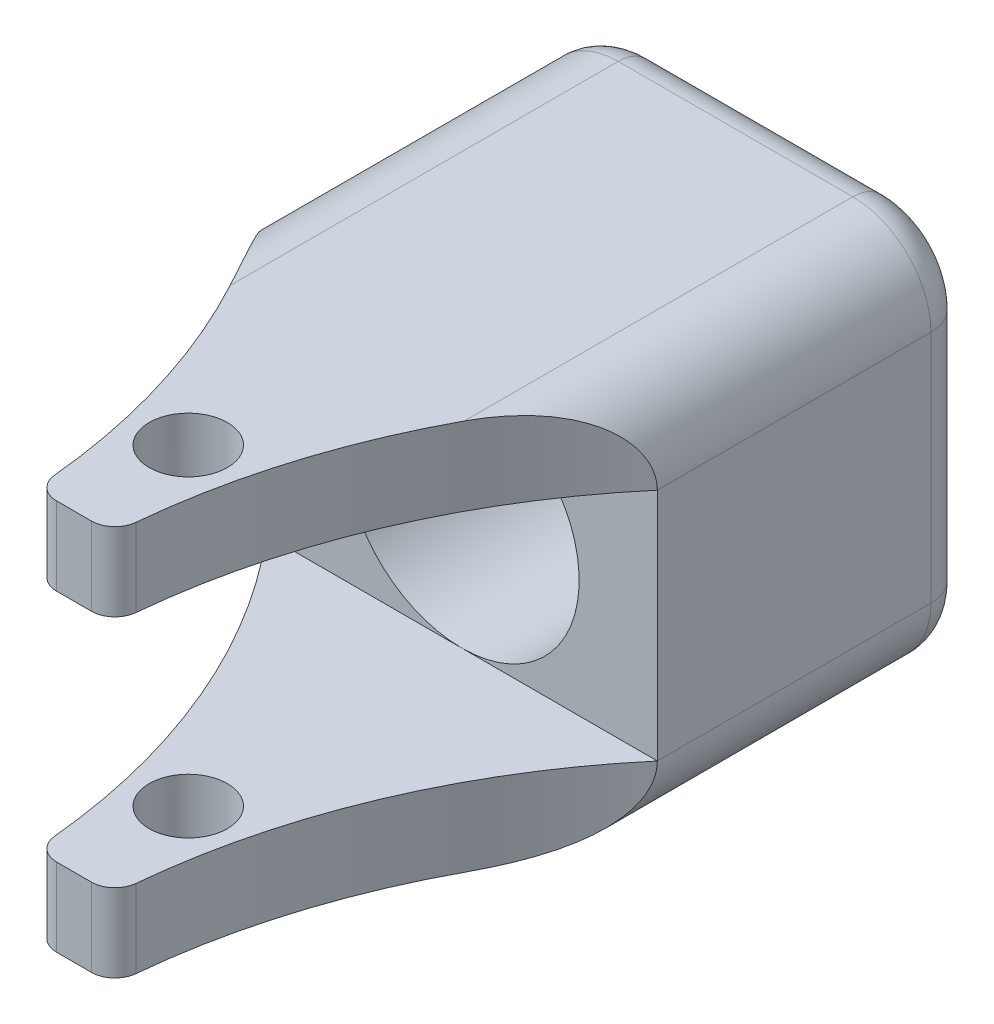
SolidWorks part; units mm, degrees
ref_plane "Front Plane" through (0, 0, 0) normal (0, 0, 1) x (1, 0, 0)
ref_plane "Top Plane" through (0, 0, 0) normal (0, 1, 0) x (1, 0, 0)
ref_plane "Right Plane" through (0, 0, 0) normal (1, 0, 0) x (0, 0, -1)
sketch "Sketch1" plane through (0, 0, 0) normal (0, 0, 1) x (1, 0, 0)
  line L1 (-25, 25) -> (25, 25)
  line L2 (-25, 25) -> (-25, -25)
  line L3 (-25, -25) -> (25, -25)
  line L4 (25, 25) -> (25, -25)
  line L5 (-25, 25) -> (25, -25) construction
  line L6 (-25, -25) -> (25, 25) construction
  point P0 (0, 0)
  dimension "D1" = 50
  dimension "D2" = 50
extrude "Boss-Extrude1" add sketch "Sketch1" along normal blind 89.61
sketch "Sketch2" plane through (0, 0, 0) normal (0, 0, -1) x (-1, 0, 0)
  circle A0 centre (0, 0) radius 15
  dimension "D1" = 30
extrude "Cut-Extrude1" cut sketch "Sketch2" against normal through all
sketch "Sketch3" plane through (-25, 0, 0) normal (-1, 0, 0) x (0, 0, 1)
  line L0 (89.61, 25) -> (89.61, -25) construction
  line L1 (40, 15) -> (89.61, 15)
  line L2 (40, 15) -> (40, -15)
  line L3 (40, -15) -> (89.61, -15)
  line L4 (89.61, 15) -> (89.61, -15)
  line L5 (40, 15) -> (89.61, -15) construction
  line L6 (40, -15) -> (89.61, 15) construction
  point P0 (64.805, 0)
  point P7 (0, 0)
  dimension "D1" = 49.61
  dimension "D2" = 30
extrude "Cut-Extrude2" cut sketch "Sketch3" against normal through all
fillet "Fillet3" radius 5 4 edges at (0, 25, 0) (25, 0, 0) (-25, 0, 0) (0, -25, 0)
fillet "Fillet4" radius 10 8 edges at (-23.5355, -23.5355, 1.4645) (23.5355, -23.5355, 1.4645) (23.5355, 23.5355, 1.4645) (-23.5355, 23.5355, 1.4645) (-25, 25, 47.305) (25, 25, 47.305) (25, -25, 47.305) (-25, -25, 47.305)
sketch "Sketch4" plane through (0, 25, 0) normal (0, 1, 0) x (1, 0, 0)
  line L0 (-2.2289, -89.61) -> (2.2289, -89.61)
  line L1 (15, -89.61) -> (-15, -89.61) construction
  circle A0 centre (0, -75) radius 5
  arc A1 (5.2153, -86.8951) -> (25, -40) centre (89.8307, -94.9726) cw
  arc A2 (-5.2153, -86.8951) -> (-25, -40) centre (-89.8307, -94.9726) ccw
  arc A3 (-2.2289, -89.61) -> (-5.2153, -86.8951) centre (-2.2289, -86.61) cw
  arc A4 (2.2289, -89.61) -> (5.2153, -86.8951) centre (2.2289, -86.61) ccw
  spline S0 degree 3 poles (-25, -40) (-88.1506, -71.433) (-33.2412, -142.0406) (62.1192, -121.0131) (53.9933, -50.2606) (25, -40) knots 0 0 0 0 0.48861 0.657386 1 1 1 1
  point P14 (0, -89.61)
  point P17 (-5, -89.61)
  point P20 (5, -89.61)
  dimension "D1" = 10
  dimension "D4" = 85
  dimension "D5" = 85
  dimension "D6" = 3
  dimension "D2" = 75
  dimension "D3" = 10
extrude "Cut-Extrude3" cut sketch "Sketch4" against normal through all
